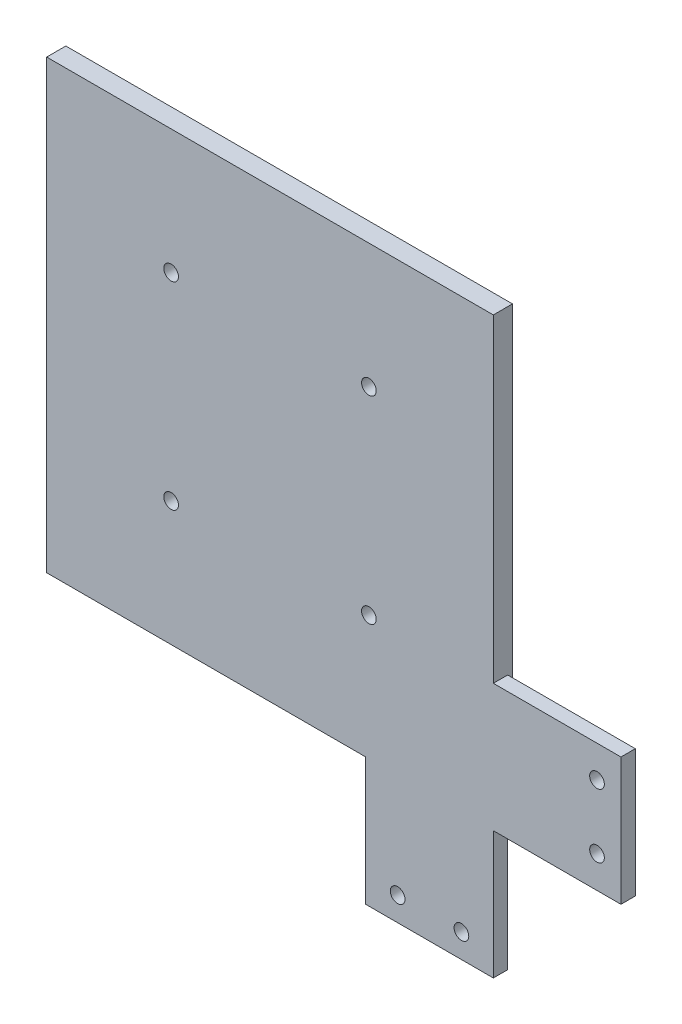
SolidWorks part; units mm, degrees
ref_plane "Front Plane" through (0, 0, 0) normal (0, 0, 1) x (1, 0, 0)
ref_plane "Top Plane" through (0, 0, 0) normal (0, 1, 0) x (1, 0, 0)
ref_plane "Right Plane" through (0, 0, 0) normal (1, 0, 0) x (0, 0, -1)
sketch "Sketch1" plane through (0, 0, -16.6) normal (0, 0, -1) x (1, 0, 0)
  line L1 (-70, -70) -> (70, -70)
  line L2 (-70, -70) -> (-70, 70)
  line L3 (-70, 70) -> (70, 70)
  line L4 (70, -70) -> (70, 70)
  line L5 (-70, -70) -> (70, 70) construction
  line L6 (-70, 70) -> (70, -70) construction
  circle A0 centre (-31, -31) radius 2.3
  circle A1 centre (-31, 31) radius 2.3
  circle A2 centre (31, 31) radius 2.3
  circle A3 centre (31, -31) radius 2.3
  point P0 (0, 0)
  point P18 (0, 0)
extrude "Boss-Extrude1" add sketch "Sketch1" along normal blind 6
sketch "Sketch2" plane through (0, 0, -16.6) normal (0, 0, 1) x (1, 0, 0)
  line L0 (30, -70) -> (70, -70)
  line L4 (70, -110) -> (30, -110)
  line L5 (30, -70) -> (30, -110)
  line L7 (70, -70) -> (70, -30)
  line L8 (70, -30) -> (110, -30)
  line L9 (110, -70) -> (110, -30)
  line L10 (70, -110) -> (70, -70)
  line L11 (70, -70) -> (110, -70)
  line L12 (50, -110) -> (50, -102.5) construction
  line L13 (50, -102.5) -> (30, -102.5) construction
  line L14 (50, -102.5) -> (50, -50) construction
  line L15 (110, -50) -> (50, -50) construction
  circle A0 centre (40, -102.5) radius 2.3
  circle A1 centre (60, -102.5) radius 2.3
  circle A2 centre (102.5, -60) radius 2.3
  circle A3 centre (102.5, -40) radius 2.3
extrude "Boss-Extrude2" add sketch "Sketch2" against normal blind 4.5 contours A0 | A1 | L10 L4 L5 L0 | L11 L9 L8 L7 | A2 | A3 region at (40, -102.5, -16.6) region at (60, -102.5, -16.6)
